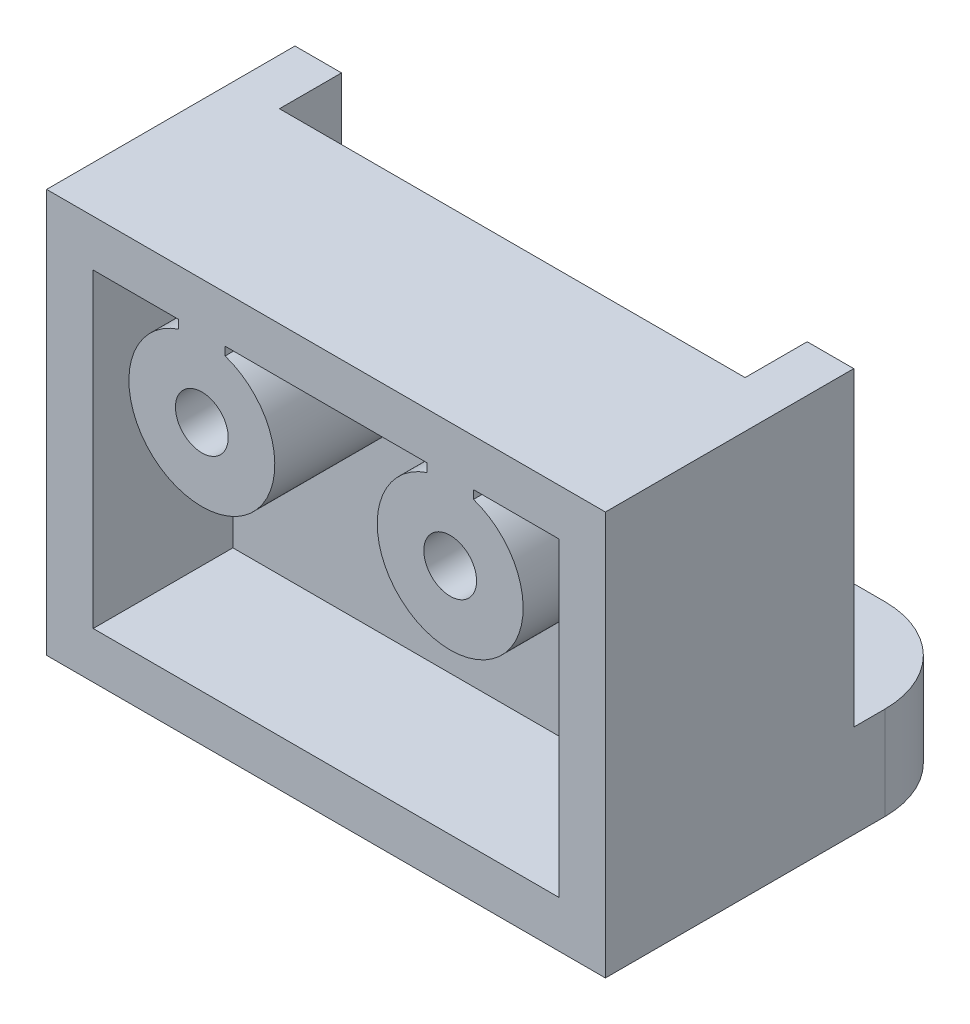
SolidWorks part; units mm, degrees
ref_plane "前视基准面" through (0, 0, 0) normal (0, 0, 1) x (1, 0, 0)
ref_plane "上视基准面" through (0, 0, 0) normal (0, 1, 0) x (1, 0, 0)
ref_plane "右视基准面" through (0, 0, 0) normal (1, 0, 0) x (0, 0, -1)
sketch "草图1" plane through (0, 0, 0) normal (0, 1, 0) x (1, 0, 0)
  line L0 (-57.4345, 0) -> (51.691, 0) construction
  line L1 (0, 59.2926) -> (0, -60.9819) construction
  line L2 (-9, 10.1) -> (-9, 0)
  line L3 (-9, 0) -> (9, 0)
  line L4 (9, 0) -> (9, 10.1)
  line L5 (9, 10.1) -> (4, 10.1)
  line L6 (-4, 10.1) -> (-4, 3)
  line L7 (-4, 3) -> (4, 3)
  line L8 (4, 3) -> (4, 10.1)
  line L13 (-4, 10.1) -> (-9, 10.1)
  dimension "D1" = 18
  dimension "D2" = 5
  dimension "D4" = 3
extrude "凸台-拉伸1" add sketch "草图1" along normal blind 30
sketch "草图2" plane through (0, 0, 0) normal (0, -1, 0) x (1, 0, 0)
  line L0 (9, 0) -> (-9, 0)
  line L1 (-9, 0) -> (-9, -28)
  line L2 (-9, -28) -> (9, -28)
  line L3 (9, -28) -> (9, 0)
  line L4 (0, -22.4608) -> (0, 12.6937) construction
  circle A0 centre (4, -25) radius 1.6
  circle A1 centre (-4, -25) radius 1.6
  dimension "D3" = 3.2
  dimension "D1" = 28
  dimension "D2" = 8
  dimension "D4" = 3
extrude "凸台-拉伸2" add sketch "草图2" along normal blind 3
sketch "草图3" plane through (0, 30, 0) normal (0, 1, 0) x (1, 0, 0)
  line L0 (-7.5, 10.1) -> (-6.4, 10.1)
  line L1 (-4, 10.1) -> (-9, 10.1) construction
  line L2 (-6.4, 10.1) -> (-6.4, 4.1)
  line L3 (-6.4, 4.1) -> (-7.5, 4.1)
  line L4 (-7.5, 4.1) -> (-7.5, 10.1)
  line L5 (-9, 10.1) -> (-9, 0) construction
  line L7 (0, 11.5268) -> (0, -2.7437) construction
  line L8 (7.5, 4.1) -> (7.5, 10.1)
  line L9 (6.4, 4.1) -> (7.5, 4.1)
  line L10 (6.4, 10.1) -> (6.4, 4.1)
  line L11 (7.5, 10.1) -> (6.4, 10.1)
  dimension "D1" = 1.5
  dimension "D2" = 1.1
  dimension "D3" = 6
extrude "切除-拉伸1" cut sketch "草图3" against normal blind 15
sketch "草图4" plane through (-9, 0, 0) normal (-1, 0, 0) x (0, 0, 1)
  line L1 (-10.1, 30) -> (-10.1, 0) construction
  line L2 (-10.1, 30) -> (0, 30) construction
  circle A0 centre (-7.1, 22.5) radius 0.9
  dimension "D1" = 1.8
  dimension "D2" = 3
  dimension "D3" = 7.5
extrude "切除-拉伸2" [suppressed] cut sketch "草图4" against normal up to surface (18 mm away) up to face at (9, 9, -12.7)
fillet "圆角1" radius 3 2 edges at (9, -1.5, -28) (-9, -1.5, -28)
sketch "草图5" plane through (-9, 0, 0) normal (-1, 0, 0) x (0, 0, 1)
  line L0 (-10.1, 0) -> (-10.1, 6)
  line L1 (-10.1, 30) -> (-10.1, 0) construction
  line L2 (-10.1, 6) -> (-15.1, 0)
  line L3 (-10.1, 0) -> (-25, 0) construction
  line L4 (-15.1, 0) -> (-10.1, 0)
  dimension "D1" = 5
  dimension "D2" = 6
extrude "凸台-拉伸3" add sketch "草图5" against normal blind 1.5
mirror "镜向1" about plane through (0, 0, 0) normal (1, 0, 0) of "凸台-拉伸3"
sketch "草图6" plane through (0, 0, 0) normal (0, 1, 0) x (1, 0, 0)
  line L0 (-4, 10.1) -> (-4, 3)
  line L1 (-4, 3) -> (4, 3)
  line L2 (4, 3) -> (4, 10.1)
  line L3 (4, 10.1) -> (-4, 10.1)
extrude "凸台-拉伸4" add sketch "草图6" along normal up to surface (30 mm away) up to face at (0, 30, -6.45)
sketch "草图7" plane through (0, 0, -10.1) normal (0, 0, -1) x (-1, 0, 0)
  line L0 (9, 30) -> (-9, 30)
  line L1 (-9, 30) -> (-9, 0)
  line L2 (-9, 0) -> (9, 0)
  line L4 (9, 30) -> (9, 6) construction
  line L6 (9, 0) -> (9, 30)
  line L7 (0, -14.0139) -> (0, 41.4977) construction
  line L9 (-7.5, 0) -> (7.5, 0) construction
  point P2 (0, 0)
  point P5 (0, 0)
  point P9 (0, 0)
extrude "切除-拉伸3" cut sketch "草图7" against normal mid plane 21
sketch "草图10" plane through (0, 0, 0) normal (0, 1, 0) x (1, 0, 0)
  line L0 (9, 16) -> (-9, 16)
  line L1 (9, 25) -> (9, 0) construction
  line L2 (-9, 0) -> (-9, 25) construction
  line L3 (-9, 16) -> (-9, 24)
  line L4 (-9, 24) -> (-7.5, 24)
  line L5 (-7.5, 24) -> (-7.5, 22)
  line L6 (-7.5, 22) -> (7.5, 22)
  line L7 (9, 16) -> (9, 24)
  line L8 (9, 24) -> (7.5, 24)
  line L9 (7.5, 24) -> (7.5, 22)
  line L10 (-6, 28) -> (6, 28) construction
  dimension "D1" = 15
  dimension "D2" = 2
  dimension "D3" = 6
  dimension "D4" = 6
extrude "凸台-拉伸5" add sketch "草图10" along normal blind 10
sketch "草图9" plane through (0, 0, -10.1) normal (0, 1, 0) x (-1, 0, 0)
  line L0 (9, 10.1) -> (-9, 10.1)
  line L2 (-9, 10.1) -> (-9, -5.9)
  line L3 (-9, -5.9) -> (9, -5.9)
  line L4 (9, -5.9) -> (9, 10.1)
  line L5 (0, -22.5385) -> (0, 65.1064) construction
extrude "切除-拉伸5" cut sketch "草图9" against normal up to next
sketch "草图11" plane through (0, 0, -22) normal (0, 0, -1) x (-1, 0, 0)
  line L0 (0, -8.2692) -> (0, 19.7312) construction
  line L2 (-7.5, 0) -> (7.5, 0) construction
  circle A0 centre (4, 6) radius 0.85
  circle A1 centre (-4, 6) radius 0.85
  dimension "D1" = 1.7
  dimension "D2" = 8
  dimension "D3" = 6
extrude "切除-拉伸6" cut sketch "草图11" against normal up to next
shell "抽壳1" thickness 1.5 removed face at (3.15, 6, -16)
shell "抽壳2" [suppressed] thickness 1.5
sketch "草图12" plane through (0, 0, -16) normal (0, 0, 1) x (1, 0, 0)
  line L0 (4, 6) -> (4, 10)
  line L1 (-9, 10) -> (9, 10) construction
  line L2 (-4, 6) -> (-4, 10)
rib "筋1" sketch "草图12" sketch "草图12" thickness 1.5 extrusion direction normal to sketch draft on no parameters "D1"=1.5
